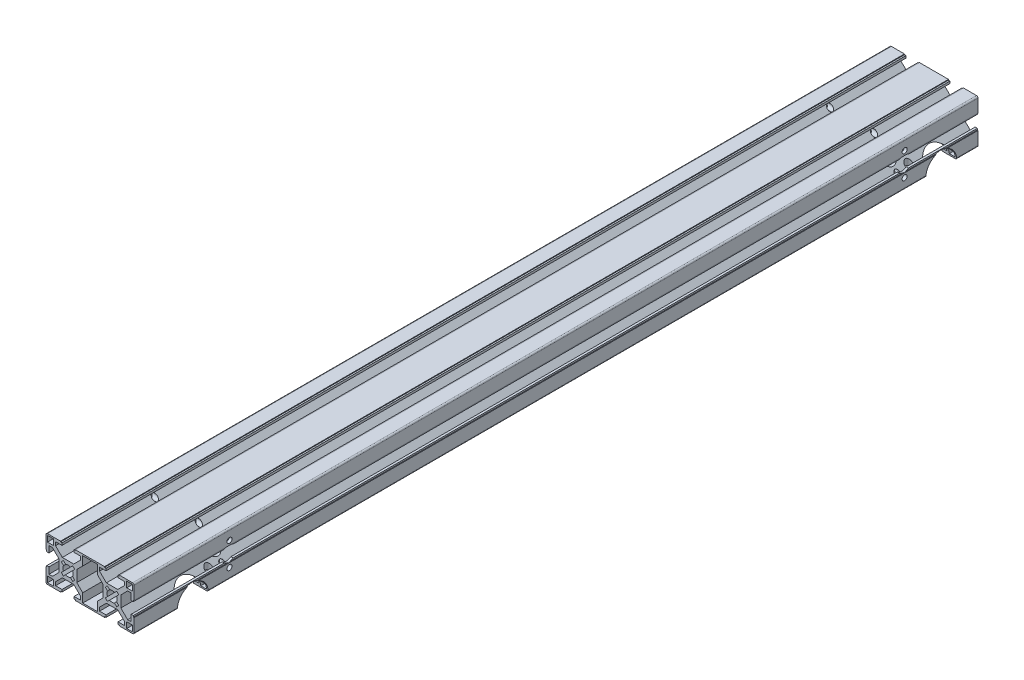
SolidWorks part; units mm, degrees
material "6063-O"
ref_plane "Plano frontal" through (0, 0, 0) normal (0, 0, 1) x (1, 0, 0)
ref_plane "Plano superior" through (0, 0, 0) normal (0, 1, 0) x (1, 0, 0)
ref_plane "Plano direito" through (0, 0, 0) normal (1, 0, 0) x (0, 0, -1)
sketch "Esboço1" plane through (0, 0, 0) normal (0, 0, 1) x (1, 0, 0)
  line L5 (0, 0) -> (-17.7944, 17.7944) construction
  line L6 (0, 3.5) -> (0, 6)
  line L8 (0, 6) -> (-3.8787, 6)
  line L9 (-3.5, 0) -> (-6, 0)
  line L48 (-6, 0) -> (-6, 3.8787)
  line L49 (-3.8787, 6) -> (-8.5, 10.6213)
  line L50 (-6, 3.8787) -> (-10.6213, 8.5)
  line L51 (0, 0) -> (-12.921, 0) construction
  line L52 (-8.5, 13) -> (-4.1, 13)
  line L53 (-4.1, 13) -> (-4.1, 14.5)
  line L54 (-4.1, 14.5) -> (-5.1, 14.5)
  line L55 (-5.1, 14.5) -> (-5.1, 15)
  line L56 (-5.1, 15) -> (-15, 15)
  line L57 (-15, 5.1) -> (-15, 15)
  line L58 (-14.5, 5.1) -> (-15, 5.1)
  line L59 (-14.5, 4.1) -> (-14.5, 5.1)
  line L60 (-13, 4.1) -> (-14.5, 4.1)
  line L61 (-13, 8.5) -> (-13, 4.1)
  line L62 (-1.6646, 3.0788) -> (-3.182, 4.5962)
  line L63 (-3.0788, 1.6646) -> (-4.5962, 3.182)
  line L64 (-4.5962, 3.182) -> (-3.182, 4.5962)
  line L65 (-8.5, 13) -> (-8.5, 10.6213)
  line L66 (-10, 14) -> (-14, 14)
  line L67 (-10, 14) -> (-10, 10)
  line L68 (-10, 10) -> (-14, 10)
  line L69 (-14, 14) -> (-14, 10)
  line L70 (-10, 14) -> (-14, 10) construction
  line L71 (-10, 10) -> (-14, 14) construction
  line L72 (-13, 8.5) -> (-10.6213, 8.5)
  circle A1 centre (0, 0) radius 3.5
  point P25 (-12, 12)
  dimension "D5" = 10.9
  dimension "D9" = 5.5
  dimension "D10" = 2
  dimension "D11" = 4
  dimension "D12" = 4
  dimension "D13" = 1
  dimension "D1" = 7
  dimension "D2" = 6
  dimension "D3" = 3
  dimension "D4" = 9.9
  dimension "D6" = 0.5
  dimension "D7" = 1.5
  dimension "D8" = 15
  dimension "D14" = 6.5
extrude "Ressalto-extrusão1" add sketch "Esboço1" along normal blind 560 contours A1 L6 L8 L49 L65 L52 L53 L54 L55 L56 L57 L58 L59 L60 L61 L72 L50 L48 L9 L63 L64 L62 L69 L66 L67 L68
sketch "Esboço3" plane through (0, 0, 0) normal (1, 0, 0) x (0, 0, -1)
  line L0 (0, 0) -> (-1000, 0) construction
  dimension "D1" = 1000
pattern_circular "PadrãoCircular1" count 4 over 360 about axis through (0, 0, 0) along (0, 0, 1) of "Ressalto-extrusão1"
pattern_linear "Padrão linear1" count 2 spacing 30 along (1, 0, 0) of "Ressalto-extrusão1", "PadrãoCircular1"
sketch "Esboço4" plane through (0, 0, 0) normal (0, 0, -1) x (-1, 0, 0)
  line L0 (-20, 14) -> (-20, -14)
  line L1 (-20, -14) -> (-10, -14)
  line L2 (-10, -14) -> (-10, 14)
  line L3 (-10, 14) -> (-20, 14)
extrude "Corte-extrusão1" cut sketch "Esboço4" against normal through all
fillet "Filete1" radius 1 4 edges at (45, -15, 280) (45, 15, 280) (-15, 15, 280) (-15, -15, 280)
sketch "Sketch1" plane through (-6, 0, 0) normal (-1, 0, 0) x (0, 0, 1)
  line L0 (0, -3.8787) -> (0, 3.8787) construction
  circle A0 centre (25, -15) radius 10.5
  point P6 (0, 0)
  dimension "D1" = 21
  dimension "D2" = 25
  dimension "D3" = 15
extrude "Cut-Extrude1" cut sketch "Sketch1" against normal through all both and the other way through all
ref_plane "Plane1" through (0, 0, 280) normal (0, 0, 1) x (1, 0, 0)
mirror "Mirror1" about plane through (0, 0, 280) normal (0, 0, 1) of "Cut-Extrude1"
sketch "Sketch2" plane through (-15, 0, 0) normal (-1, 0, 0) x (0, 0, 1)
  circle A0 centre (25, -15) radius 4
  circle A1 centre (535, -15) radius 4
  dimension "D1" = 8
  dimension "D2" = 8
sketch "Sketch4" plane through (45, 0, 0) normal (1, 0, 0) x (0, 0, -1)
  circle A0 centre (-25, -15) radius 10.7346
  circle A1 centre (-535, -15) radius 8.2077
ref_plane "Plane4" through (15, 0, 0) normal (-1, 0, 0) x (0, 0, 1)
ref_plane "Plane2" through (0, 0, 0) normal (0, -1, 0) x (-1, 0, 0)
ref_plane "Plane3" through (15, 0, 0) normal (-1, 0, 0) x (0, 0, 1)
sketch "Sketch5" plane through (-15, 0, 0) normal (-1, 0, 0) x (0, 0, 1)
  line L0 (0, -3.8787) -> (0, 3.8787) construction
  line L1 (280, 14) -> (280, -14) construction
  line L2 (560, 14) -> (0, 14) construction
  line L3 (35.4523, -14) -> (524.5477, -14) construction
  circle A0 centre (50, 0) radius 4
  circle A5 centre (50, -8) radius 1.75
  circle A6 centre (42, 0) radius 1.75
  circle A7 centre (50, 8) radius 1.75
  circle A8 centre (58, 0) radius 1.75
  circle A9 centre (502, 0) radius 1.75
  circle A10 centre (510, 8) radius 1.75
  circle A11 centre (518, 0) radius 1.75
  circle A12 centre (510, -8) radius 1.75
  circle A13 centre (510, 0) radius 4
  point P13 (50, 0)
  dimension "D1" = 8
  dimension "D2" = 0
  dimension "D3" = 8
  dimension "D5" = 3.5
  dimension "D4" = 50
  dimension "D6" = 0
  dimension "D7" = 4
extrude "Cut-Extrude2" cut sketch "Sketch5" against normal through all
sketch "Sketch6" plane through (-15, 0, 0) normal (-1, 0, 0) x (0, 0, 1)
  line L0 (280, 14) -> (280, -14) construction
  line L1 (560, 14) -> (0, 14) construction
  line L2 (35.4523, -14) -> (524.5477, -14) construction
  circle A0 centre (50, 0) radius 5.1
  circle A1 centre (510, 0) radius 5.1
  dimension "D1" = 10.2
extrude "Cut-Extrude3" cut sketch "Sketch6" against normal blind 10
mirror "Mirror2" about plane through (15, 0, 0) normal (-1, 0, 0) of "Cut-Extrude3"
sketch "Sketch8" plane through (0, -15, 0) normal (0, -1, 0) x (1, 0, 0)
  line L0 (39.55, 524.5) -> (39.55, 518.5) construction
  line L1 (35.1, 524.5) -> (44, 524.5) construction
  line L2 (20.45, 524.5) -> (20.45, 518.5) construction
  line L3 (5.1, 524.5) -> (24.9, 524.5) construction
  line L4 (9.55, 524.5) -> (9.55, 518.5) construction
  line L5 (24.9, 524.5) -> (24.9, 35.5) construction
  line L6 (5.1, 524.5) -> (5.1, 35.5) construction
  line L7 (-9.55, 524.5) -> (-9.55, 518.5) construction
  line L8 (-5.1, 524.5) -> (-14, 524.5) construction
  line L9 (44, 280) -> (-14, 280) construction
  line L10 (44, 35.5) -> (44, 524.5) construction
  line L11 (-14, 524.5) -> (-14, 35.5) construction
  circle A0 centre (-9.55, 518.5) radius 2.5
  circle A1 centre (9.55, 518.5) radius 2.5
  circle A2 centre (20.45, 518.5) radius 2.5
  circle A3 centre (39.55, 518.5) radius 2.5
  circle A4 centre (-9.55, 41.5) radius 2.5
  circle A5 centre (9.55, 41.5) radius 2.5
  circle A6 centre (20.45, 41.5) radius 2.5
  circle A7 centre (39.55, 41.5) radius 2.5
  dimension "D7" = 5
  dimension "D8" = 5
  dimension "D9" = 5
  dimension "D10" = 5
  dimension "D1" = 4.45
  dimension "D2" = 4.45
  dimension "D3" = 6
  dimension "D4" = 6
  dimension "D5" = 6
  dimension "D6" = 6
extrude "Cut-Extrude4" cut sketch "Sketch8" against normal blind 15
sketch "Sketch9" plane through (0, 0, 560) normal (0, 0, 1) x (1, 0, 0)
  line L0 (35.1, 15) -> (35.1, 14.5)
  line L1 (35.1, 14.5) -> (34.1, 14.5)
  line L2 (34.1, 14.5) -> (34.1, 13)
  line L3 (34.1, 13) -> (38.5, 13)
  line L4 (38.5, 13) -> (38.5, 10.6213)
  line L5 (38.5, 10.6213) -> (33.8787, 6)
  line L6 (33.8787, 6) -> (26.1213, 6)
  line L7 (26.1213, 6) -> (21.5, 10.6213)
  line L8 (21.5, 10.6213) -> (21.5, 13)
  line L9 (21.5, 13) -> (25.9, 13)
  line L10 (25.9, 13) -> (25.9, 14.5)
  line L11 (25.9, 14.5) -> (24.9, 14.5)
  line L12 (24.9, 14.5) -> (24.9, 15)
  line L13 (24.9, 15) -> (5.1, 15)
  line L14 (5.1, 15) -> (5.1, 14.5)
  line L15 (4.1, 14.5) -> (5.1, 14.5) construction
  line L16 (5.1, 14.5) -> (5.1, 15) construction
  line L17 (5.1, 14.5) -> (4.1, 14.5)
  line L18 (4.1, 14.5) -> (4.1, 13)
  line L19 (4.1, 13) -> (8.5, 13)
  line L20 (8.5, 13) -> (8.5, 10.6213)
  line L21 (8.5, 10.6213) -> (3.8787, 6)
  line L22 (3.8787, 6) -> (-3.8787, 6)
  line L23 (-3.8787, 6) -> (-8.5, 10.6213)
  line L24 (-8.5, 10.6213) -> (-8.5, 13)
  line L25 (-8.5, 13) -> (-4.1, 13)
  line L26 (-4.1, 13) -> (-4.1, 14.5)
  line L27 (-4.1, 14.5) -> (-5.1, 14.5)
  line L28 (-5.1, 14.5) -> (-5.1, 15)
  line L29 (-5.1, 15) -> (-14, 15)
  line L30 (-15, 14) -> (-15, 5.1)
  line L31 (-15, 5.1) -> (-14.5, 5.1)
  line L32 (-14.5, 5.1) -> (-14.5, 4.1)
  line L33 (-14.5, 4.1) -> (-13, 4.1)
  line L34 (-13, 4.1) -> (-13, 8.5)
  line L35 (-13, 8.5) -> (-10.6213, 8.5)
  line L36 (-10.6213, 8.5) -> (-6, 3.8787)
  line L37 (-6, 3.8787) -> (-6, -3.8787)
  line L38 (35.1, 15) -> (44, 15) construction
  line L39 (44, 15) -> (35.1, 15)
  line L40 (45, 14) -> (45, 5.1)
  line L41 (45, 5.1) -> (44.5, 5.1)
  line L42 (44.5, 5.1) -> (44.5, 4.1)
  line L43 (44.5, 4.1) -> (43, 4.1)
  line L44 (43, 4.1) -> (43, 8.5)
  line L45 (43, 8.5) -> (40.6213, 8.5)
  line L46 (40.6213, 8.5) -> (36, 3.8787)
  line L47 (36, 3.8787) -> (36, -3.8787)
  line L48 (44, 14) -> (44, 10)
  line L49 (44, 10) -> (40, 10)
  line L50 (40, 10) -> (40, 14)
  line L51 (40, 14) -> (44, 14)
  line L52 (24, -3.8787) -> (24, 3.8787)
  line L53 (24, 3.8787) -> (20, 7.8787)
  line L54 (20, 7.8787) -> (20, 14)
  line L55 (20, 14) -> (10, 14)
  line L56 (10, 14) -> (10, 7.8787)
  line L57 (10, 7.8787) -> (6, 3.8787)
  line L59 (3.182, 4.5962) -> (1.6646, 3.0788)
  line L60 (-14, 14) -> (-10, 14)
  line L61 (-14, 14) -> (-14, 10)
  line L62 (-14, 10) -> (-10, 10)
  line L63 (-10, 14) -> (-10, 10)
  line L64 (3.182, 4.5962) -> (4.5962, 3.182)
  line L65 (-4.5962, -3.182) -> (-3.182, -4.5962)
  line L66 (4.5962, 3.182) -> (3.0788, 1.6646)
  line L67 (4.5962, -3.182) -> (3.0788, -1.6646)
  line L68 (4.5962, -3.182) -> (3.182, -4.5962)
  line L69 (-3.182, 4.5962) -> (-4.5962, 3.182)
  line L70 (3.182, -4.5962) -> (1.6646, -3.0788)
  line L71 (4.5962, 3.182) -> (3.0788, 1.6646)
  line L72 (-1.6646, 3.0788) -> (-3.182, 4.5962)
  line L73 (-4.5962, 3.182) -> (-3.0788, 1.6646)
  line L75 (-3.0788, -1.6646) -> (-4.5962, -3.182)
  line L78 (31.6646, 3.0788) -> (33.182, 4.5962)
  line L79 (33.182, 4.5962) -> (34.5962, 3.182)
  line L80 (34.5962, 3.182) -> (33.0788, 1.6646)
  line L81 (33.0788, -1.6646) -> (34.5962, -3.182)
  line L82 (34.5962, -3.182) -> (33.182, -4.5962)
  line L83 (33.182, -4.5962) -> (31.6646, -3.0788)
  line L84 (28.3354, -3.0788) -> (26.818, -4.5962)
  line L85 (26.818, -4.5962) -> (25.4038, -3.182)
  line L86 (25.4038, -3.182) -> (26.9212, -1.6646)
  line L87 (28.3354, 3.0788) -> (26.818, 4.5962)
  line L88 (26.818, 4.5962) -> (25.4038, 3.182)
  line L89 (25.4038, 3.182) -> (26.9212, 1.6646)
  line L90 (36, 0) -> (-6, 0) construction
  line L93 (-10.6213, -8.5) -> (-6, -3.8787)
  line L94 (40.6213, -8.5) -> (36, -3.8787)
  line L95 (43, -4.1) -> (43, -8.5)
  line L96 (44.5, -4.1) -> (43, -4.1)
  line L97 (44.5, -5.1) -> (44.5, -4.1)
  line L98 (45, -5.1) -> (44.5, -5.1)
  line L99 (45, -14) -> (45, -5.1)
  line L100 (20, -7.8787) -> (20, -14)
  line L101 (24, -3.8787) -> (20, -7.8787)
  line L102 (40, -14) -> (44, -14)
  line L103 (40, -10) -> (40, -14)
  line L104 (44, -10) -> (40, -10)
  line L105 (44, -14) -> (44, -10)
  line L106 (43, -8.5) -> (40.6213, -8.5)
  line L107 (44, -15) -> (35.1, -15)
  line L108 (24.9, -14.5) -> (24.9, -15)
  line L109 (25.9, -14.5) -> (24.9, -14.5)
  line L110 (25.9, -13) -> (25.9, -14.5)
  line L111 (21.5, -13) -> (25.9, -13)
  line L112 (21.5, -10.6213) -> (21.5, -13)
  line L113 (26.1213, -6) -> (21.5, -10.6213)
  line L114 (33.8787, -6) -> (26.1213, -6)
  line L115 (38.5, -10.6213) -> (33.8787, -6)
  line L116 (38.5, -13) -> (38.5, -10.6213)
  line L117 (34.1, -13) -> (38.5, -13)
  line L118 (34.1, -14.5) -> (34.1, -13)
  line L119 (35.1, -14.5) -> (34.1, -14.5)
  line L120 (35.1, -15) -> (35.1, -14.5)
  line L121 (24.9, -15) -> (5.1, -15)
  line L122 (20, -14) -> (10, -14)
  line L123 (10, -7.8787) -> (6, -3.8787)
  line L124 (-10, -14) -> (-10, -10)
  line L125 (-14, -10) -> (-10, -10)
  line L126 (-14, -14) -> (-14, -10)
  line L127 (-14, -14) -> (-10, -14)
  line L128 (10, -14) -> (10, -7.8787)
  line L129 (-13, -8.5) -> (-10.6213, -8.5)
  line L130 (-13, -4.1) -> (-13, -8.5)
  line L131 (-14.5, -4.1) -> (-13, -4.1)
  line L132 (-14.5, -5.1) -> (-14.5, -4.1)
  line L133 (-15, -5.1) -> (-14.5, -5.1)
  line L134 (-15, -14) -> (-15, -5.1)
  line L135 (-5.1, -15) -> (-14, -15)
  line L136 (-5.1, -14.5) -> (-5.1, -15)
  line L137 (-4.1, -14.5) -> (-5.1, -14.5)
  line L138 (-4.1, -13) -> (-4.1, -14.5)
  line L139 (-8.5, -13) -> (-4.1, -13)
  line L140 (-8.5, -10.6213) -> (-8.5, -13)
  line L141 (-3.8787, -6) -> (-8.5, -10.6213)
  line L142 (3.8787, -6) -> (-3.8787, -6)
  line L143 (8.5, -10.6213) -> (3.8787, -6)
  line L144 (8.5, -13) -> (8.5, -10.6213)
  line L145 (4.1, -13) -> (8.5, -13)
  line L146 (4.1, -14.5) -> (4.1, -13)
  line L147 (5.1, -14.5) -> (4.1, -14.5)
  line L148 (5.1, -15) -> (5.1, -14.5)
  line L149 (6, 3.8787) -> (6, -3.8787)
  line L150 (-3.182, -4.5962) -> (-1.6653, -3.0785)
  arc A0 (-14, 15) -> (-15, 14) centre (-14, 14) ccw
  arc A1 (-14, 15) -> (-15, 14) centre (-14, 14) ccw construction
  arc A2 (45, 14) -> (44, 15) centre (44, 14) ccw
  arc A3 (1.6646, 3.0788) -> (-1.6646, 3.0788) centre (0, 0) ccw
  arc A4 (-3.0788, 1.6646) -> (-3.0788, -1.6646) centre (0, 0) ccw
  arc A5 (-1.6653, -3.0785) -> (1.6646, -3.0788) centre (0, 0) ccw
  arc A6 (3.0788, -1.6646) -> (3.0788, 1.6646) centre (0, 0) ccw
  arc A7 (-1.6646, -3.0788) -> (1.6646, -3.0788) centre (0, 0) ccw construction
  arc A8 (1.6646, 3.0788) -> (-1.6646, 3.0788) centre (0, 0) ccw construction
  arc A9 (-3.0788, 1.6646) -> (-3.0788, -1.6646) centre (0, 0) ccw construction
  arc A10 (31.6646, 3.0788) -> (28.3354, 3.0788) centre (30, 0) ccw
  arc A11 (33.0788, -1.6646) -> (33.0788, 1.6646) centre (30, 0) ccw
  arc A12 (28.3354, -3.0788) -> (31.6646, -3.0788) centre (30, 0) ccw
  arc A13 (26.9212, 1.6646) -> (26.9212, -1.6646) centre (30, 0) ccw
  arc A14 (45, -14) -> (44, -15) centre (44, -14) cw
  arc A15 (-14, -15) -> (-15, -14) centre (-14, -14) cw
  dimension "D1" = 2
extrude "Boss-Extrude1" add sketch "Sketch9" along normal blind 15
